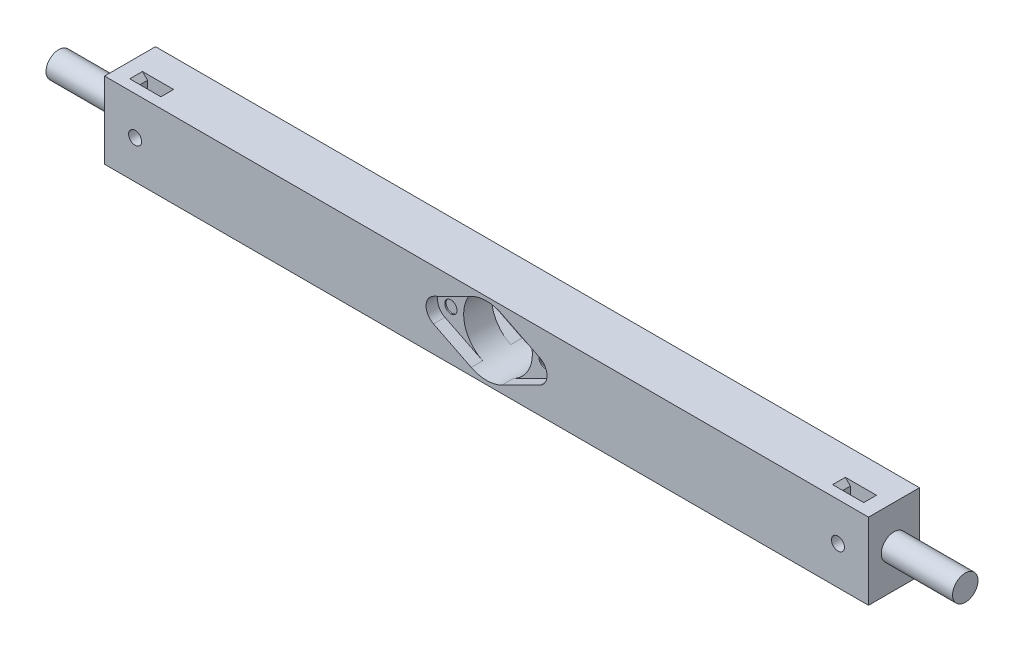
SolidWorks part; units mm, degrees
ref_plane "前视基准面" through (0, 0, 0) normal (0, 0, 1) x (1, 0, 0)
ref_plane "上视基准面" through (0, 0, 0) normal (0, 1, 0) x (1, 0, 0)
ref_plane "右视基准面" through (0, 0, 0) normal (1, 0, 0) x (0, 0, -1)
other "Configuration Table"
sketch "草图1" plane through (0, 0, 0) normal (0, 0, 1) x (1, 0, 0)
  line L0 (0, 0) -> (79.8665, 0) construction
  line L1 (0, 0) -> (0, 25.0088) construction
  line L2 (-150, 0) -> (-150, 30)
  line L3 (-150, 30) -> (150, 30)
  line L4 (150, 30) -> (150, 0)
  line L5 (150, 0) -> (-150, 0)
  point P7 (0, 30)
  dimension "D1" = 300
  dimension "D2" = 30
extrude "凸台-拉伸1" add sketch "草图1" along normal blind 20 contours L2 L3 L4 L5
sketch "草图2" plane through (-150, 0, 0) normal (-1, 0, 0) x (0, 0, 1)
  line L0 (0, 0) -> (0, 30) construction
  line L1 (0, 0) -> (0, 30) construction
  line L3 (0, 15) -> (20, 15) construction
  line L6 (0, 20) -> (0, 10)
  arc A0 (0, 10) -> (0, 20) centre (0, 15) ccw
  dimension "D1" = 5
sketch "草图3" plane through (0, 0, 0) normal (0, 0, -1) x (-1, 0, 0)
  line L0 (0, 0) -> (0, 129.1579) construction
  line L1 (-178, 15) -> (178, 15) construction
  line L2 (-6.0203, 27.0833) -> (-20.8412, 19.6991)
  line L3 (6.0203, 27.0833) -> (20.8412, 19.6991)
  line L4 (6.0203, 2.9167) -> (20.8412, 10.3009)
  line L5 (-6.0203, 2.9167) -> (-20.8412, 10.3009)
  circle A0 centre (0, 15) radius 4
  circle A1 centre (0, 15) radius 6
  circle A2 centre (0, 15) radius 13.25
  circle A3 centre (18.5, 15) radius 2.4
  circle A4 centre (0, 15) radius 13.5
  circle A5 centre (-18.5, 15) radius 2.4
  arc A6 (-20.8412, 19.6991) -> (-20.8412, 10.3009) centre (-18.5, 15) ccw
  arc A7 (20.8412, 19.6991) -> (20.8412, 10.3009) centre (18.5, 15) cw
  point P20 (-23.75, 15)
  dimension "D1" = 8
  dimension "D2" = 2
  dimension "D4" = 4.8
  dimension "D6" = 0.25
  dimension "D7" = 10.5
  dimension "D5" = 18.5
  dimension "D3" = 7.25
extrude "切除-拉伸1" cut sketch "草图3" against normal through all contours A0 region at (0, 15, 0)
extrude "切除-拉伸2" cut sketch "草图3<3>" against normal through all contours A1 A0 region at (5.8303, 15, 0)
sketch "草图3<3>" plane through (0, 0, 0) normal (0, 0, -1) x (-1, 0, 0) same geometry as "草图3"
extrude "切除-拉伸3" cut sketch "草图3<4>" against normal through all contours A2 A1 | A4 A2 region at (0, 28.4618, 0) region at (12.8752, 15, 0)
sketch "草图3<4>" plane through (0, 0, 0) normal (0, 0, -1) x (-1, 0, 0) same geometry as "草图3"
extrude "切除-拉伸4" cut sketch "草图3<5>" against normal blind 4.5 contours L2 A6 L5 A4 A5 | A7 L3 A4 L4 A3 region at (13.7997, 15, 0) region at (-13.2971, 23.1229, 0)
sketch "草图3<5>" plane through (0, 0, 0) normal (0, 0, -1) x (-1, 0, 0) same geometry as "草图3"
extrude "切除-拉伸5" cut sketch "草图3<6>" against normal blind 5 contours A5 | A3 region at (-18.5, 15, 0) region at (18.5, 15, 0)
sketch "草图3<6>" plane through (0, 0, 0) normal (0, 0, -1) x (-1, 0, 0) same geometry as "草图3"
sketch "草图4" plane through (-150, 0, 0) normal (-1, 0, 0) x (0, 0, 1)
  line L0 (20, 30) -> (0, 0) construction
  line L1 (0, -200000) -> (0, 200030) construction
  circle A0 centre (10, 15) radius 5
extrude "凸台-拉伸2" add sketch "草图4" along normal blind 28
ref_plane "基准面1" through (0, 0, 0) normal (-1, 0, 0) x (0, 0, 1)
mirror "镜向1" about plane through (0, 0, 0) normal (-1, 0, 0) of "凸台-拉伸2"
sketch "草图5" plane through (0, 0, 20) normal (0, 0, 1) x (1, 0, 0)
  line L0 (-138, 30) -> (-138, 0) construction
  line L1 (-150, 30) -> (150, 30) construction
  line L2 (-150, -200000) -> (-150, 200030) construction
  line L4 (150, 0) -> (-150, 0) construction
  circle A0 centre (-138, 15) radius 2.55
  dimension "D1" = 12
extrude "切除-拉伸6" cut sketch "草图5" against normal blind 4 contours A0
sketch "草图6" plane through (0, 0, 16) normal (0, 0, 1) x (1, 0, 0)
  line L0 (-138, 17.55) -> (-138, 12.45) construction
  line L1 (150, 0) -> (-150, 0) construction
  line L2 (-142.1085, 30) -> (-133.8915, 30)
  line L3 (-142.1085, 30) -> (-142.1085, 0)
  line L4 (-142.1085, 0) -> (-133.8915, 0)
  line L5 (-133.8915, 30) -> (-133.8915, 0)
  line L6 (-142.1085, 30) -> (-133.8915, 0) construction
  line L7 (-142.1085, 0) -> (-133.8915, 30) construction
  line L8 (-150, 30) -> (150, 30) construction
  circle A0 centre (-138, 15) radius 2.55 construction
  point P5 (-138, 15)
extrude "切除-拉伸7" cut sketch "草图6" against normal blind 5 contours L5 L4 L3 L2
chamfer "倒角1" distance 2 angle 45 4 edges at (-133.8915, 0, 13.5) (-142.1085, 0, 13.5) (-133.8915, 30, 13.5) (-142.1085, 30, 13.5)
mirror "镜向2" about plane through (0, 0, 0) normal (-1, 0, 0) of "倒角1", "切除-拉伸7", "切除-拉伸6"
ref_plane "基准面2" through (0, 0, 10) normal (0, 0, 1) x (1, 0, 0)
mirror "镜向3" about plane through (0, 0, 10) normal (0, 0, 1) of "切除-拉伸4", "切除-拉伸5"
